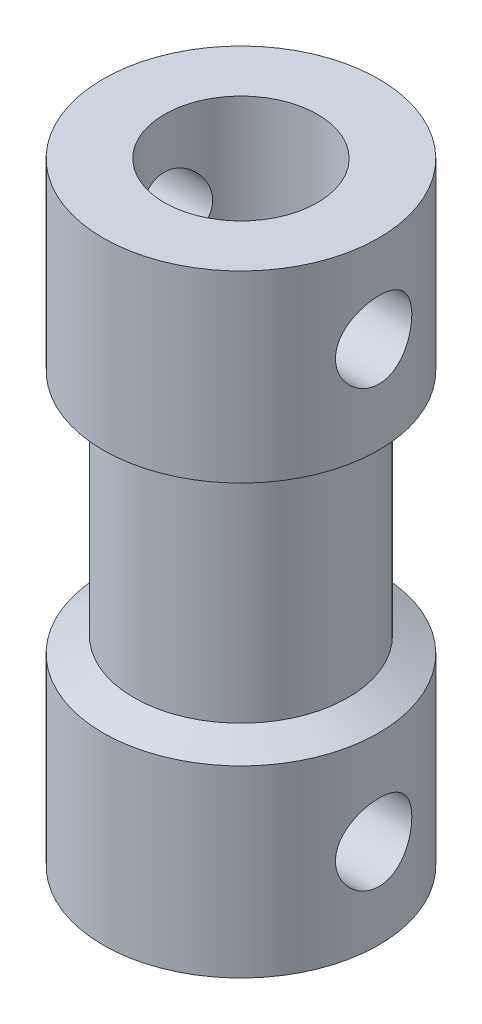
SolidWorks part; units mm, degrees
material "易切削黄铜, UNS C36000"
ref_plane "前视基准面" through (0, 0, 0) normal (0, 0, 1) x (1, 0, 0)
ref_plane "上视基准面" through (0, 0, 0) normal (0, 1, 0) x (1, 0, 0)
ref_plane "右视基准面" through (0, 0, 0) normal (1, 0, 0) x (0, 0, -1)
sketch "草图1" plane through (0, 0, 0) normal (0, 1, 0) x (1, 0, 0)
  circle A0 centre (0, 0) radius 4.5
  circle A1 centre (0, 0) radius 2.5
  dimension "D1" = 9
  dimension "D2" = 5
extrude "凸台-拉伸1" add sketch "草图1" along normal blind 6.5
sketch "草图2" plane through (0, 6.5, 0) normal (0, 1, 0) x (1, 0, 0)
  circle A0 centre (0, 0) radius 3.5
  dimension "D1" = 7
extrude "凸台-拉伸2" add sketch "草图2" along normal blind 7
sketch "草图3" plane through (0, 13.5, 0) normal (0, 1, 0) x (1, 0, 0)
  circle A0 centre (0, 0) radius 4.5
  circle A1 centre (0, 0) radius 2.5
  dimension "D1" = 9
  dimension "D2" = 5
extrude "凸台-拉伸3" add sketch "草图3" along normal blind 6.5
chamfer "倒角1" distance 0.5 distance2 1 1 edges at (0, 6.5, 4.5) first distance on face at (0, 6.5, 4.5)
chamfer "倒角2" distance 1 distance2 0.5 1 edges at (0, 13.5, 4.5) first distance on face at (0, 13.5, 3.5)
hole_wizard "M3 螺纹孔1" positions "3D草图1" profile "草图4" tap size "M3" standard "GB" end condition through all
sketch3d "3D草图1"
  point P0 (4.5, 2.9047, -0.0105)
sketch "草图4" plane through (4.5, 2.9047, -0.0105) normal (0, 1, 0) x (-0.0023, 0, -1)
  line L0 (0, 0) -> (0, 9.0105)
  line L1 (0, 9.0105) -> (1.25, 9.0105)
  line L2 (1.25, 9.0105) -> (1.25, 0)
  line L5 (1.25, 0) -> (0, 0)
  line L11 (0, -6.35) -> (0, 107.95) construction
  dimension "通孔螺纹孔钻头直径" = 2.5
  dimension "通孔螺纹孔钻头深度" = 9.0105
cosmetic thread "孔螺蚊线1" parameters "D2"=3
hole_wizard "M3 螺纹孔2" positions "3D草图2" profile "草图5" tap size "M3" standard "GB" end condition through all
sketch3d "3D草图2"
  point P0 (4.5, 17.1163, -0.0105)
sketch "草图5" plane through (4.5, 17.1163, -0.0105) normal (0, 1, 0) x (-0.0023, 0, -1)
  line L0 (0, 0) -> (0, 9.0105)
  line L1 (0, 9.0105) -> (1.25, 9.0105)
  line L2 (1.25, 9.0105) -> (1.25, 0)
  line L5 (1.25, 0) -> (0, 0)
  line L11 (0, -6.35) -> (0, 107.95) construction
  dimension "通孔螺纹孔钻头直径" = 2.5
  dimension "通孔螺纹孔钻头深度" = 9.0105
cosmetic thread "孔螺蚊线2" parameters "D2"=3
